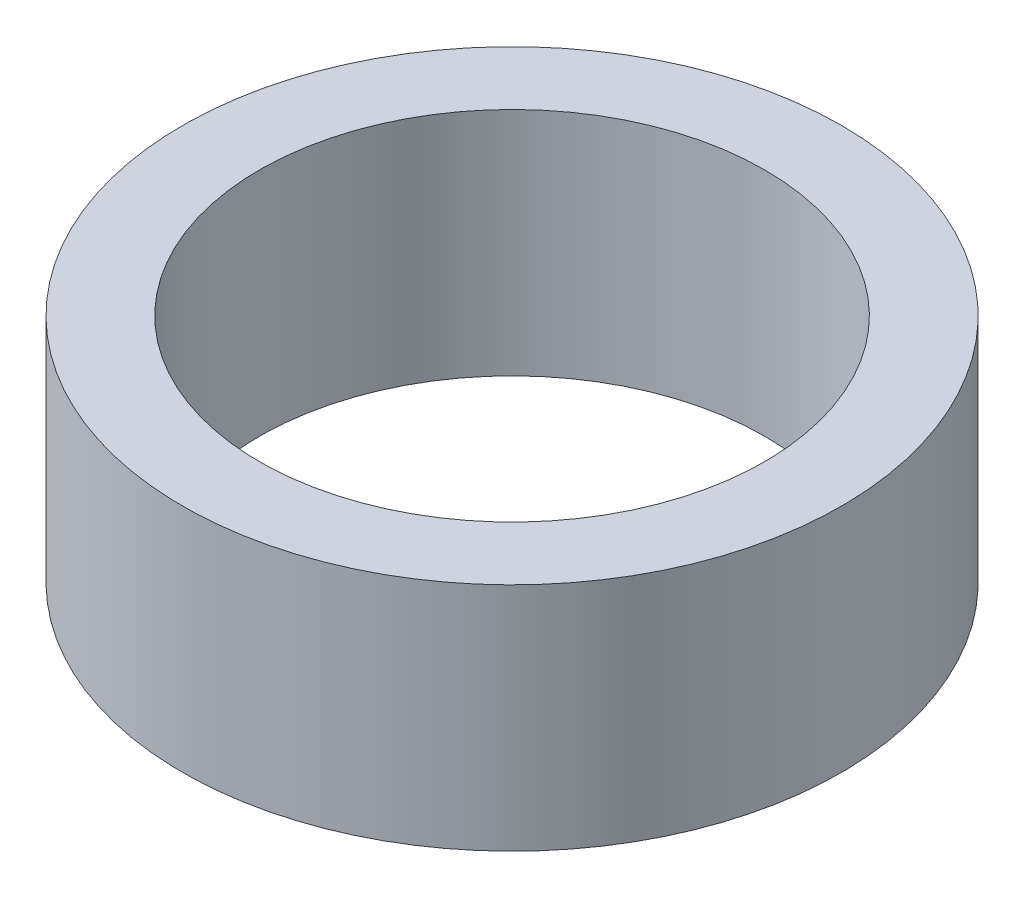
SolidWorks part; units mm, degrees
material "聚亚安酯(11671)"
ref_plane "前视基准面" through (0, 0, 0) normal (0, 0, 1) x (1, 0, 0)
ref_plane "上视基准面" through (0, 0, 0) normal (0, 1, 0) x (1, 0, 0)
ref_plane "右视基准面" through (0, 0, 0) normal (1, 0, 0) x (0, 0, -1)
sketch "草图1" plane through (0, 0, 0) normal (0, 1, 0) x (1, 0, 0)
  circle A0 centre (0, 0) radius 30
  circle A1 centre (0, 0) radius 23
  dimension "D1" = 60
  dimension "D2" = 46
extrude "凸台-拉伸1" add sketch "草图1" along normal blind 21
